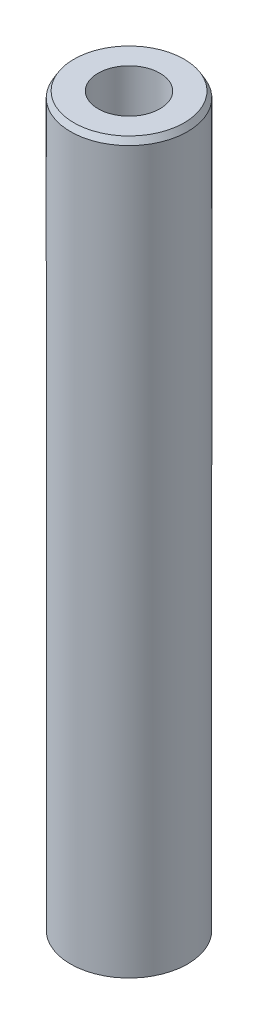
SolidWorks part; units mm, degrees
ref_plane "Front Plane" through (0, 0, 0) normal (0, 0, 1) x (1, 0, 0)
ref_plane "Top Plane" through (0, 0, 0) normal (0, 1, 0) x (1, 0, 0)
ref_plane "Right Plane" through (0, 0, 0) normal (1, 0, 0) x (0, 0, -1)
sketch "Sketch1" plane through (0, 0, 0) normal (0, 1, 0) x (1, 0, 0)
  circle A0 centre (0, 0) radius 15
  dimension "SHAFT_OD" = 30
extrude "Boss-Extrude1" add sketch "Sketch1" along normal blind 187.0343
sketch "Sketch2" plane through (0, 0, 0) normal (0, 1, 0) x (1, 0, 0)
  circle A0 centre (0, 0) radius 7.9162
  dimension "BORE_D" = 15.8324
extrude "Cut-Extrude1" cut sketch "Sketch2" along normal through all
chamfer "Chamfer1" distance 1.5196 angle 30 2 edges at (0, 187.0343, 15) (0, 0, 15) first distance on face at (0, 187.0343, 15) first distance on face at (0, 0, 7.9162)
